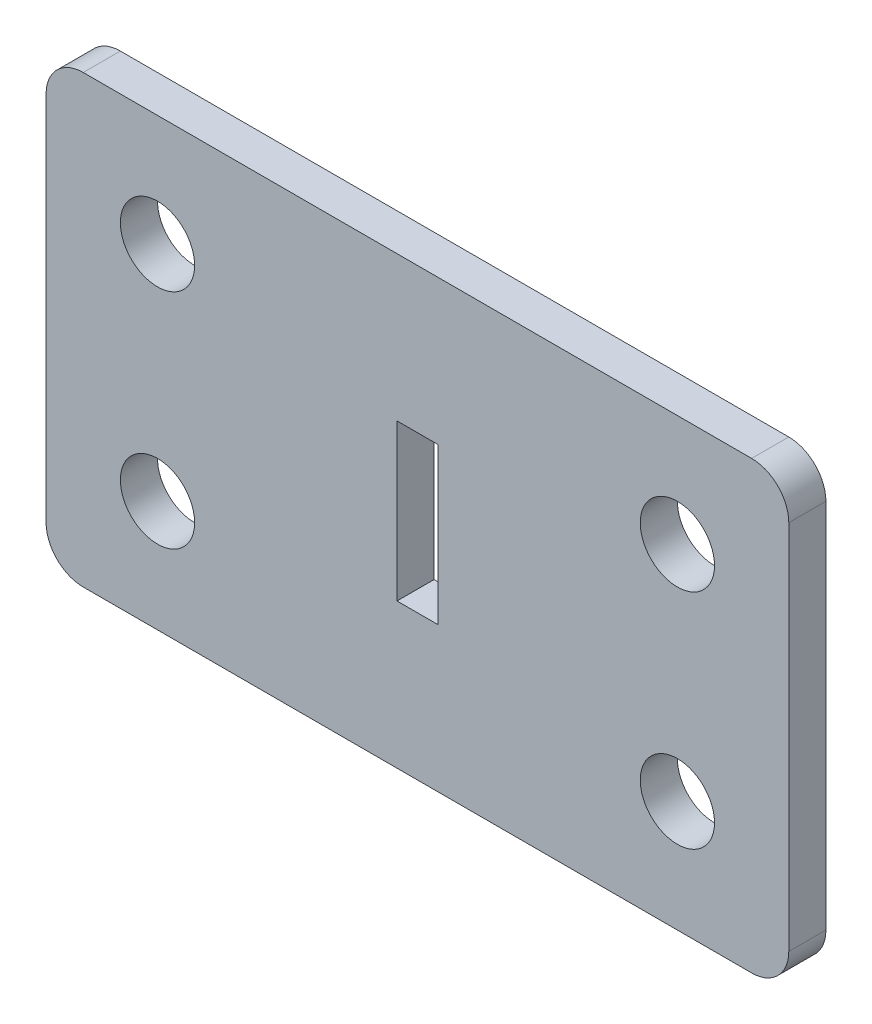
SolidWorks part; units mm, degrees
ref_plane "Ön Düzlem" through (0, 0, 0) normal (0, 0, 1) x (1, 0, 0)
ref_plane "Üst Düzlem" through (0, 0, 0) normal (0, 1, 0) x (1, 0, 0)
ref_plane "Sağ Düzlem" through (0, 0, 0) normal (1, 0, 0) x (0, 0, -1)
sketch "Çizim1" plane through (0, 0, 0) normal (0, 0, 1) x (1, 0, 0)
  line L1 (-50, 30) -> (50, 30)
  line L2 (-50, 30) -> (-50, -30)
  line L3 (-50, -30) -> (50, -30)
  line L4 (50, 30) -> (50, -30)
  line L5 (-50, 30) -> (50, -30) construction
  line L6 (-50, -30) -> (50, 30) construction
  point P0 (0, 0)
  dimension "D1" = 100
  dimension "D2" = 60
base flange "Taban-Flanş1" sketch "Çizim1" thickness 5 reverse thickness direction no parameters "D1"=4
fillet "Radyus1" radius 5 4 edges at (50, -30, -2.5) (-50, -30, -2.5) (-50, 30, -2.5) (50, 30, -2.5)
sketch "Çizim6" plane through (0, 0, 0) normal (0, 0, 1) x (1, 0, 0)
  line L1 (-35, 15) -> (35, 15) construction
  line L2 (-35, 15) -> (-35, -15) construction
  line L3 (-35, -15) -> (35, -15) construction
  line L4 (35, 15) -> (35, -15) construction
  line L5 (-35, 15) -> (35, -15) construction
  line L6 (-35, -15) -> (35, 15) construction
  circle A0 centre (-35, 15) radius 5
  circle A1 centre (-35, -15) radius 5
  circle A2 centre (35, 15) radius 5
  circle A3 centre (35, -15) radius 5
  point P0 (0, 0)
  dimension "D3" = 10
  dimension "D1" = 30
  dimension "D2" = 70
extrude "Kes-Ekstrüzyon1" cut sketch "Çizim6" against normal blind 10
sketch "Çizim7" plane through (0, 0, -5) normal (0, 0, -1) x (-1, 0, 0)
  line L1 (-2.75, 10.5) -> (2.75, 10.5)
  line L2 (-2.75, 10.5) -> (-2.75, -10.5)
  line L3 (-2.75, -10.5) -> (2.75, -10.5)
  line L4 (2.75, 10.5) -> (2.75, -10.5)
  line L5 (-2.75, 10.5) -> (2.75, -10.5) construction
  line L6 (-2.75, -10.5) -> (2.75, 10.5) construction
  point P0 (0, 0)
  dimension "D1" = 21
  dimension "D2" = 5.5
extrude "Kes-Ekstrüzyon2" cut sketch "Çizim7" against normal blind 10
sketch "Büküm-Çizgileri1" [suppressed] plane through (0, 0, 0) normal (0, 1, 0) x (1, 0, 0)
sketch "Sınırlandırma-Kutusu1" [suppressed] plane through (0, 0, 0) normal (0, 1, 0) x (1, 0, 0)
sheet metal parameters "Sac-Levha1" thickness 5 parameters "D1"=4
flat pattern "Düz-Çoğaltma1" [suppressed]
sketch "Büküm-Çizgileri2" plane through (0, 0, 0) normal (0, 1, 0) x (1, 0, 0)
sketch3d "Sınırlandırma-Kutusu2" [suppressed]
  line L0 (-50, 30, 0) -> (50, 30, 0) construction
  line L1 (-50, -30, 0) -> (50, -30, 0) construction
  line L2 (-50, 30, 0) -> (-50, -30, 0) construction
  line L3 (50, 30, 0) -> (50, -30, 0) construction
sheet metal parameters "Sac-Levha2" thickness 5 parameters "D1"=4
flat pattern "Düz-Çoğaltma1"
sketch "Büküm-Çizgileri2" plane through (0, 0, 0) normal (0, 1, 0) x (1, 0, 0)
sketch3d "Sınırlandırma-Kutusu2" [suppressed]
  line L0 (-50, 30, 0) -> (50, 30, 0) construction
  line L1 (-50, -30, 0) -> (50, -30, 0) construction
  line L2 (-50, 30, 0) -> (-50, -30, 0) construction
  line L3 (50, 30, 0) -> (50, -30, 0) construction
sheet metal parameters "Sac-Levha3" thickness 5 parameters "D1"=4
flat pattern "Düz-Çoğaltma1"
sketch "Büküm-Çizgileri2" plane through (0, 0, 0) normal (0, 1, 0) x (1, 0, 0)
sketch3d "Sınırlandırma-Kutusu2" [suppressed]
  line L0 (-50, 30, 0) -> (50, 30, 0) construction
  line L1 (-50, -30, 0) -> (50, -30, 0) construction
  line L2 (-50, 30, 0) -> (-50, -30, 0) construction
  line L3 (50, 30, 0) -> (50, -30, 0) construction
